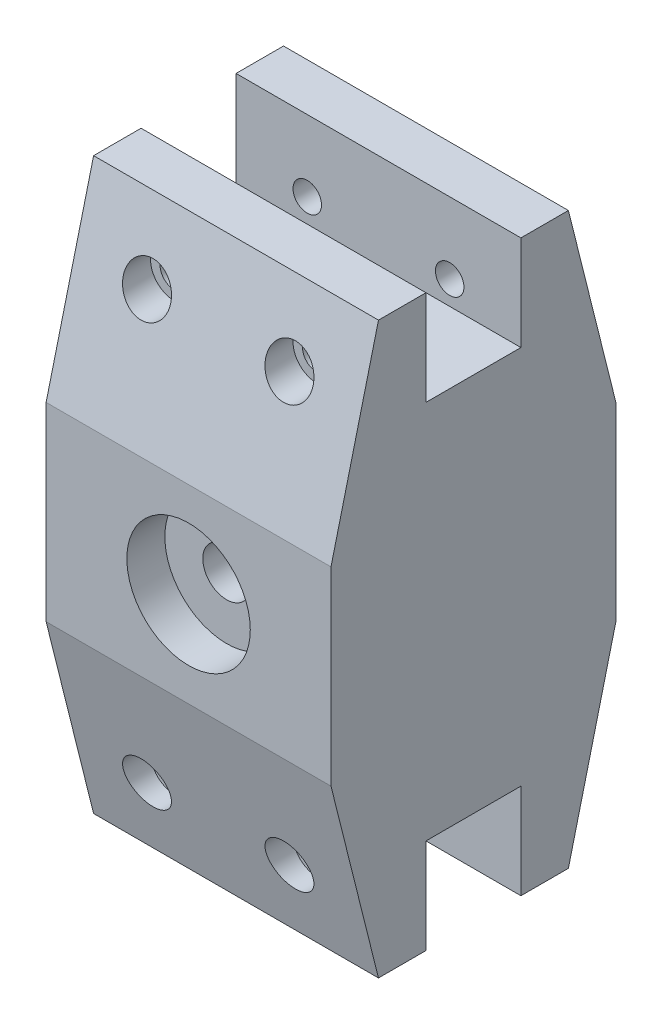
SolidWorks part; units mm, degrees
material "ABS"
ref_plane "Front Plane" through (0, 0, 0) normal (0, 0, 1) x (1, 0, 0)
ref_plane "Top Plane" through (0, 0, 0) normal (0, 1, 0) x (1, 0, 0)
ref_plane "Right Plane" through (0, 0, 0) normal (1, 0, 0) x (0, 0, -1)
sketch "Sketch2" plane through (0, 0, 0) normal (1, 0, 0) x (0, 0, -1)
  line L0 (30, 120) -> (30, 0) construction
  line L1 (0, 0) -> (60, 0)
  line L2 (0, 0) -> (0, 120)
  line L3 (0, 120) -> (60, 120)
  line L4 (60, 0) -> (60, 120)
  line L5 (30, 0) -> (60, 60) construction
  line L6 (60, 60) -> (0, 60) construction
  line L7 (0, 80) -> (10, 120)
  line L8 (60, 80) -> (50, 120)
  line L9 (60, 40) -> (50, 0)
  line L10 (0, 40) -> (10, 0)
  line L11 (20, 20) -> (40, 20)
  line L12 (20, 140) -> (40, 140)
  line L13 (20, 140) -> (20, 100)
  line L14 (20, 100) -> (40, 100)
  line L15 (40, 140) -> (40, 100)
  line L16 (20, 140) -> (40, 100) construction
  line L17 (20, 100) -> (40, 140) construction
  line L18 (40, -20) -> (40, 20)
  line L19 (20, -20) -> (40, -20)
  line L20 (20, -20) -> (20, 20)
  dimension "D1" = 60
  dimension "D2" = 120
  dimension "D3" = 20
  dimension "D4" = 20
  dimension "D5" = 20
  dimension "D6" = 20
extrude "Boss-Extrude1" add sketch "Sketch2" along normal blind 60 contours L2 L10 L1 L9 L4 L8 L3 L7 region at (0, 60, -30)
sketch "Sketch3" plane through (0, 0, 0) normal (0, 0, 1) x (1, 0, 0)
  line L0 (0, 60) -> (60, 60) construction
  line L1 (0, 40) -> (0, 80) construction
  line L2 (60, 40) -> (60, 80) construction
  line L3 (60, 60) -> (30, 120) construction
  line L4 (60, 120) -> (0, 120) construction
  line L5 (30, 120) -> (30, -5.0282) construction
  circle A0 centre (30, 60) radius 5
  dimension "D1" = 10
extrude "Cut-Extrude1" cut sketch "Sketch3" against normal blind 70
ref_plane "Plane1" through (0, 0, -30) normal (0, 0, 1) x (1, 0, 0)
sketch "Sketch4" plane through (0, 0, 0) normal (0, 0, 1) x (1, 0, 0)
  circle A0 centre (30, 60) radius 13
  dimension "D1" = 26
extrude "Cut-Extrude2" cut sketch "Sketch4" against normal blind 8
mirror "Mirror1" about plane through (0, 0, -30) normal (0, 0, 1) of "Cut-Extrude2"
sketch "Sketch5" plane through (0, 0, 0) normal (0, 0, 1) x (1, 0, 0)
  line L0 (30, 60) -> (89.4194, 60) construction
  line L1 (89.4194, 60) -> (-15.9572, 60) construction
  line L2 (-15.9572, 60) -> (30, 60) construction
  line L3 (30, 60) -> (30, 132.1461) construction
  line L4 (60, 120) -> (0, 120) construction
  circle A0 centre (45, 105) radius 3
  circle A1 centre (15, 105) radius 3
  circle A2 centre (45, 15) radius 3
  circle A3 centre (15, 15) radius 3
  dimension "D1" = 6
  dimension "D2" = 15
  dimension "D3" = 15
extrude "Cut-Extrude3" cut sketch "Sketch5" against normal through all
sketch "Sketch6" plane through (0, 0, 0) normal (0, 0, 1) x (1, 0, 0)
  line L0 (30, 120) -> (30, -1.9963) construction
  line L1 (60, 120) -> (0, 120) construction
  line L2 (30, -1.9963) -> (60, 60) construction
  line L3 (60, 40) -> (60, 80) construction
  line L4 (60, 60) -> (-4.5066, 60) construction
  circle A0 centre (45, 105) radius 500000
  circle A1 centre (45, 105) radius 5
  circle A2 centre (15, 105) radius 5
  circle A3 centre (15, 15) radius 5
  circle A4 centre (45, 15) radius 5
  dimension "D1" = 1000000
  dimension "D2" = 10
extrude "Cut-Extrude4" cut sketch "Sketch6" against normal blind 12 contours A2 | A1 | A3 | A4
mirror "Mirror2" about plane through (0, 0, -30) normal (0, 0, 1) of "Cut-Extrude4"
